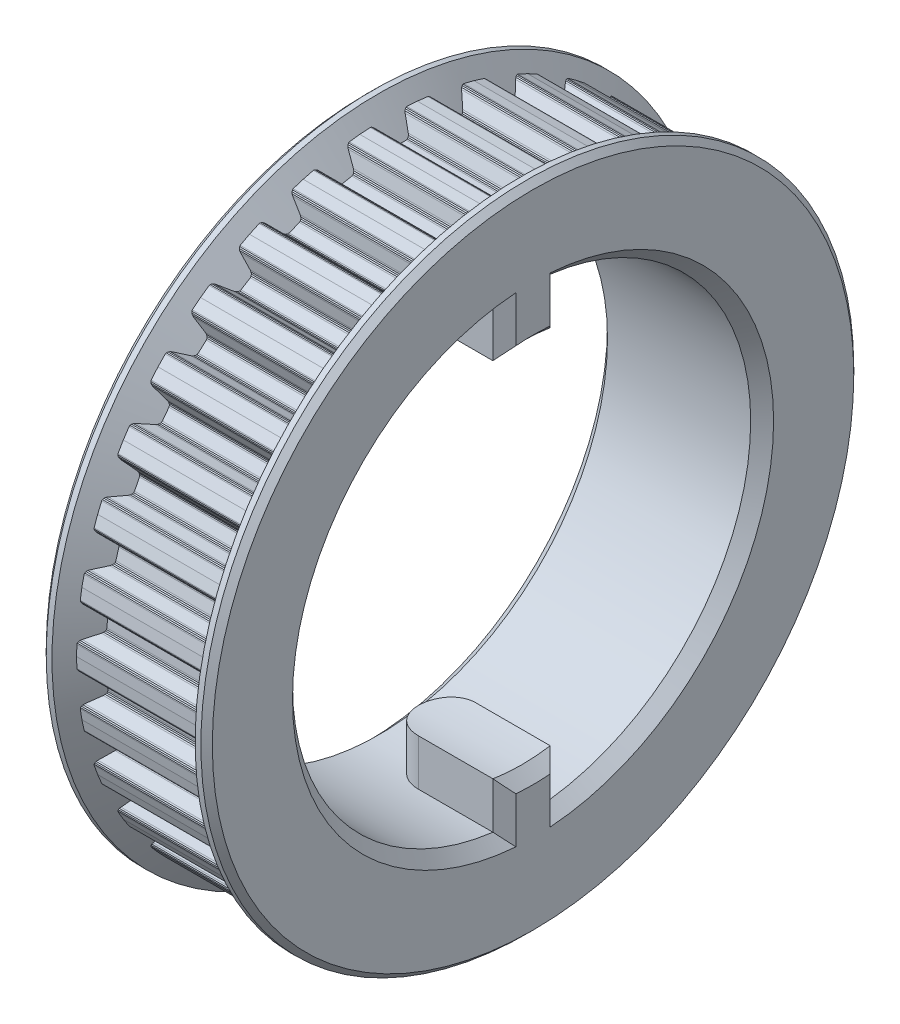
SolidWorks part; units mm, degrees
material "PLA"
ref_plane "Front Plane" through (0, 0, 0) normal (0, 0, 1) x (1, 0, 0)
ref_plane "Top Plane" through (0, 0, 0) normal (0, 1, 0) x (1, 0, 0)
ref_plane "Right Plane" through (0, 0, 0) normal (1, 0, 0) x (0, 0, -1)
sketch "Sketch1" plane through (0, 0, 0) normal (1, 0, 0) x (0, 0, -1)
  circle A1 centre (0, 0) radius 25.5
  dimension "D2" = 51
extrude "Boss-Extrude1" add sketch "Sketch1" along normal mid plane 12.5
sketch "Sketch2" plane through (6.25, 0, 0) normal (1, 0, 0) x (0, 0, -1)
  circle A7 centre (0, 0) radius 28.5
  circle A8 centre (0, 0) radius 28.5
  dimension "D1" = 3
extrude "Boss-Extrude2" add sketch "Sketch2" along normal blind 1
mirror "Mirror2" about plane through (0, 0, 0) normal (1, 0, 0) of "Boss-Extrude2"
sketch "Sketch3" plane through (7.25, 0, 0) normal (1, 0, 0) x (0, 0, -1)
  circle A0 centre (0, 0) radius 20
  dimension "D1" = 40
extrude "Cut-Extrude1" cut sketch "Sketch3" against normal through all
sketch "Sketch5" plane through (7.25, 0, 0) normal (1, 0, 0) x (0, 0, -1)
  line L1 (2.5, 28.3901) -> (-2.5, 28.3901)
  line L2 (2.5, 28.3901) -> (2.5, -28.3901)
  line L3 (2.5, -28.3901) -> (-2.5, -28.3901)
  line L4 (-2.5, 28.3901) -> (-2.5, -28.3901)
  line L5 (2.5, 28.3901) -> (-2.5, -28.3901) construction
  line L6 (2.5, -28.3901) -> (-2.5, 28.3901) construction
  circle A0 centre (0, 0) radius 28.5 construction
  circle A1 centre (0, 0) radius 16
  circle A2 centre (0, 0) radius 20 construction
  point P0 (0, 0)
  circle M5 centre (0, 0) radius 20
  dimension "D2" = 4
  dimension "D1" = 5
extrude "Boss-Extrude3" add sketch "Sketch5" against normal blind 10 contours A1 L4 L2 M5 | A1 L2 L4 M5 region at (7.25, 17.9411, 0) region at (7.25, -17.9411, 0)
fillet "Fillet1" radius 2.5 4 edges at (-2.75, 17.8233, 2.5) (-2.75, 17.8233, -2.5) (-2.75, -17.8233, -2.5) (-2.75, -17.8233, 2.5)
chamfer "Chamfer1" distance 3 angle 35 2 edges at (6.25, 0, -25.5) (-6.25, 0, -25.5) first distance on face at (6.25, 0, -25.5) first distance on face at (-6.25, 0, -25.5)
chamfer "Chamfer4" distance 1 angle 45 9 edges at (-7.25, 0, -20) (7.25, 0, 20) (7.25, 0, -20) (7.25, 17.8233, -2.5) (7.25, 16, 0) (7.25, 17.8233, 2.5) (7.25, -17.8233, 2.5) (7.25, -16, 0) (7.25, -17.8233, -2.5)
chamfer "Chamfer3" distance 0.5 angle 45 2 edges at (-7.25, 0, -28.5) (7.25, 0, -28.5)
sketch "Sketch6" plane through (0, 0, 0) normal (1, 0, 0) x (0, 0, -1)
  line L0 (2.5129, -27.119) -> (3.4233, -27.0134)
  line L1 (3.4233, -27.0134) -> (3.5073, -26.9837)
  line L2 (3.5073, -26.9837) -> (3.5995, -26.9145)
  line L3 (3.5995, -26.9145) -> (3.6697, -26.8197)
  line L4 (3.6697, -26.8197) -> (3.7127, -26.7044)
  line L5 (3.7127, -26.7044) -> (3.9415, -25.6841)
  line L6 (3.9415, -25.6841) -> (3.9845, -25.5692)
  line L7 (3.9845, -25.5692) -> (4.0547, -25.4743)
  line L8 (4.0547, -25.4743) -> (4.147, -25.4049)
  line L9 (4.147, -25.4049) -> (4.2565, -25.3661)
  line L10 (4.2565, -25.3661) -> (5.1942, -25.1908)
  line L11 (5.1942, -25.1908) -> (5.3104, -25.1874)
  line L12 (5.3104, -25.1874) -> (5.4215, -25.2188)
  line L13 (5.4215, -25.2188) -> (5.5212, -25.282)
  line L14 (5.5212, -25.282) -> (5.6028, -25.3736)
  line L15 (5.6028, -25.3736) -> (6.1847, -26.2423)
  line L16 (6.1847, -26.2423) -> (6.2666, -26.3342)
  line L17 (6.2666, -26.3342) -> (6.3663, -26.3973)
  line L18 (6.3663, -26.3973) -> (6.4774, -26.4285)
  line L19 (6.4774, -26.4285) -> (6.5663, -26.4259)
  line L20 (6.5663, -26.4259) -> (7.4533, -26.1955)
  line L21 (7.4533, -26.1955) -> (8.3287, -25.9245)
  line L22 (8.3287, -25.9245) -> (8.4058, -25.8798)
  line L23 (8.4058, -25.8798) -> (8.4838, -25.7948)
  line L24 (8.4838, -25.7948) -> (8.5353, -25.6887)
  line L25 (8.5353, -25.6887) -> (8.5564, -25.5675)
  line L26 (8.5564, -25.5675) -> (8.5939, -24.5226)
  line L27 (8.5939, -24.5226) -> (8.615, -24.4017)
  line L28 (8.615, -24.4017) -> (8.6665, -24.2956)
  line L29 (8.6665, -24.2956) -> (8.7445, -24.2103)
  line L30 (8.7445, -24.2103) -> (8.845, -24.152)
  line L31 (8.845, -24.152) -> (9.7346, -23.8074)
  line L32 (9.7346, -23.8074) -> (9.8481, -23.7828)
  line L33 (9.8481, -23.7828) -> (9.9632, -23.7932)
  line L34 (9.9632, -23.7932) -> (10.0727, -23.837)
  line L35 (10.0727, -23.837) -> (10.1698, -23.912)
  line L36 (10.1698, -23.912) -> (10.9014, -24.659)
  line L37 (10.9014, -24.659) -> (10.9988, -24.7344)
  line L38 (10.9988, -24.7344) -> (11.1084, -24.778)
  line L39 (11.1084, -24.778) -> (11.2233, -24.7883)
  line L40 (11.2233, -24.7883) -> (11.3102, -24.7694)
  line L41 (11.3102, -24.7694) -> (12.1398, -24.38)
  line L42 (12.1398, -24.38) -> (12.9505, -23.9527)
  line L43 (12.9505, -23.9527) -> (13.0181, -23.8946)
  line L44 (13.0181, -23.8946) -> (13.0791, -23.7967)
  line L45 (13.0791, -23.7967) -> (13.1103, -23.683)
  line L46 (13.1103, -23.683) -> (13.1087, -23.5599)
  line L47 (13.1087, -23.5599) -> (12.9536, -22.5259)
  line L48 (12.9536, -22.5259) -> (12.9521, -22.4032)
  line L49 (12.9521, -22.4032) -> (12.9833, -22.2894)
  line L50 (12.9833, -22.2894) -> (13.0443, -22.1913)
  line L51 (13.0443, -22.1913) -> (13.1323, -22.1155)
  line L52 (13.1323, -22.1155) -> (13.9434, -21.6133)
  line L53 (13.9434, -21.6133) -> (14.0505, -21.5683)
  line L54 (14.0505, -21.5683) -> (14.1655, -21.5574)
  line L55 (14.1655, -21.5574) -> (14.2813, -21.5802)
  line L56 (14.2813, -21.5802) -> (14.3905, -21.6362)
  line L57 (14.3905, -21.6362) -> (15.2469, -22.236)
  line L58 (15.2469, -22.236) -> (15.3564, -22.2922)
  line L59 (15.3564, -22.2922) -> (15.4722, -22.315)
  line L60 (15.4722, -22.315) -> (15.5871, -22.304)
  line L61 (15.5871, -22.304) -> (15.669, -22.2694)
  line L62 (15.669, -22.2694) -> (16.4129, -21.7342)
  line L63 (16.4129, -21.7342) -> (17.1313, -21.1652)
  line L64 (17.1313, -21.1652) -> (17.1871, -21.0957)
  line L65 (17.1871, -21.0957) -> (17.229, -20.9883)
  line L66 (17.229, -20.9883) -> (17.2388, -20.8707)
  line L67 (17.2388, -20.8707) -> (17.2147, -20.75)
  line L68 (17.2147, -20.75) -> (16.8721, -19.7621)
  line L69 (16.8721, -19.7621) -> (16.8482, -19.6418)
  line L70 (16.8482, -19.6418) -> (16.8579, -19.5242)
  line L71 (16.8579, -19.5242) -> (16.8998, -19.4166)
  line L72 (16.8998, -19.4166) -> (16.9724, -19.3259)
  line L73 (16.9724, -19.3259) -> (17.6775, -18.6832)
  line L74 (17.6775, -18.6832) -> (17.7744, -18.6192)
  line L75 (17.7744, -18.6192) -> (17.8855, -18.5874)
  line L76 (17.8855, -18.5874) -> (18.0034, -18.5886)
  line L77 (18.0034, -18.5886) -> (18.1211, -18.6236)
  line L78 (18.1211, -18.6236) -> (19.0731, -19.0558)
  line L79 (19.0731, -19.0558) -> (19.1911, -19.0909)
  line L80 (19.1911, -19.0909) -> (19.3091, -19.092)
  line L81 (19.3091, -19.092) -> (19.42, -19.0601)
  line L82 (19.42, -19.0601) -> (19.4942, -19.0111)
  line L83 (19.4942, -19.0111) -> (20.1271, -18.3483)
  line L84 (20.1271, -18.3483) -> (20.7287, -17.6569)
  line L85 (20.7287, -17.6569) -> (20.7707, -17.5784)
  line L86 (20.7707, -17.5784) -> (20.7923, -17.4651)
  line L87 (20.7923, -17.4651) -> (20.7802, -17.3477)
  line L88 (20.7802, -17.3477) -> (20.7344, -17.2335)
  line L89 (20.7344, -17.2335) -> (20.2161, -16.3254)
  line L90 (20.2161, -16.3254) -> (20.1705, -16.2115)
  line L91 (20.1705, -16.2115) -> (20.1584, -16.0942)
  line L92 (20.1584, -16.0942) -> (20.1798, -15.9806)
  line L93 (20.1798, -15.9806) -> (20.2346, -15.8782)
  line L94 (20.2346, -15.8782) -> (20.8095, -15.1169)
  line L95 (20.8095, -15.1169) -> (20.8931, -15.0362)
  line L96 (20.8931, -15.0362) -> (20.9964, -14.9845)
  line L97 (20.9964, -14.9845) -> (21.1126, -14.964)
  line L98 (21.1126, -14.964) -> (21.2346, -14.9767)
  line L99 (21.2346, -14.9767) -> (22.2499, -15.2267)
  line L100 (22.2499, -15.2267) -> (22.3723, -15.2395)
  line L101 (22.3723, -15.2395) -> (22.4885, -15.2189)
  line L102 (22.4885, -15.2189) -> (22.5916, -15.1671)
  line L103 (22.5916, -15.1671) -> (22.6556, -15.1053)
  line L104 (22.6556, -15.1053) -> (23.1559, -14.3375)
  line L105 (23.1559, -14.3375) -> (23.6202, -13.5474)
  line L106 (23.6202, -13.5474) -> (23.6471, -13.4625)
  line L107 (23.6471, -13.4625) -> (23.6474, -13.3471)
  line L108 (23.6474, -13.3471) -> (23.614, -13.234)
  line L109 (23.614, -13.234) -> (23.548, -13.1301)
  line L110 (23.548, -13.1301) -> (22.8717, -12.3327)
  line L111 (22.8717, -12.3327) -> (22.8059, -12.2292)
  line L112 (22.8059, -12.2292) -> (22.7725, -12.116)
  line L113 (22.7725, -12.116) -> (22.7727, -12.0005)
  line L114 (22.7727, -12.0005) -> (22.8077, -11.8897)
  line L115 (22.8077, -11.8897) -> (23.2329, -11.0357)
  line L116 (23.2329, -11.0357) -> (23.3002, -10.9411)
  line L117 (23.3002, -10.9411) -> (23.3923, -10.8713)
  line L118 (23.3923, -10.8713) -> (23.5027, -10.8298)
  line L119 (23.5027, -10.8298) -> (23.625, -10.8199)
  line L120 (23.625, -10.8199) -> (24.6689, -10.879)
  line L121 (24.6689, -10.879) -> (24.7916, -10.8691)
  line L122 (24.7916, -10.8691) -> (24.902, -10.8275)
  line L123 (24.902, -10.8275) -> (24.9939, -10.7577)
  line L124 (24.9939, -10.7577) -> (25.0454, -10.6852)
  line L125 (25.0454, -10.6852) -> (25.3961, -9.8385)
  line L126 (25.3961, -9.8385) -> (25.7073, -8.9765)
  line L127 (25.7073, -8.9765) -> (25.7182, -8.8881)
  line L128 (25.7182, -8.8881) -> (25.6973, -8.7746)
  line L129 (25.6973, -8.7746) -> (25.6437, -8.6696)
  line L130 (25.6437, -8.6696) -> (25.5597, -8.5797)
  line L131 (25.5597, -8.5797) -> (24.7484, -7.9201)
  line L132 (24.7484, -7.9201) -> (24.6647, -7.8304)
  line L133 (24.6647, -7.8304) -> (24.611, -7.7253)
  line L134 (24.611, -7.7253) -> (24.59, -7.6117)
  line L135 (24.59, -7.6117) -> (24.604, -7.4964)
  line L136 (24.604, -7.4964) -> (24.8651, -6.5788)
  line L137 (24.8651, -6.5788) -> (24.9139, -6.4734)
  line L138 (24.9139, -6.4734) -> (24.9916, -6.3879)
  line L139 (24.9916, -6.3879) -> (25.0925, -6.3267)
  line L140 (25.0925, -6.3267) -> (25.2109, -6.2946)
  line L141 (25.2109, -6.2946) -> (26.2479, -6.1609)
  line L142 (26.2479, -6.1609) -> (26.3667, -6.1286)
  line L143 (26.3667, -6.1286) -> (26.4676, -6.0674)
  line L144 (26.4676, -6.0674) -> (26.5451, -5.9819)
  line L145 (26.5451, -5.9819) -> (26.5824, -5.9011)
  line L146 (26.5824, -5.9011) -> (26.7715, -5.0045)
  line L147 (26.7715, -5.0045) -> (26.9191, -4.1)
  line L148 (26.9191, -4.1) -> (26.9135, -4.0111)
  line L149 (26.9135, -4.0111) -> (26.8721, -3.9034)
  line L150 (26.8721, -3.9034) -> (26.8001, -3.81)
  line L151 (26.8001, -3.81) -> (26.701, -3.737)
  line L152 (26.701, -3.737) -> (25.7823, -3.2377)
  line L153 (25.7823, -3.2377) -> (25.6835, -3.1649)
  line L154 (25.6835, -3.1649) -> (25.6115, -3.0715)
  line L155 (25.6115, -3.0715) -> (25.57, -2.9637)
  line L156 (25.57, -2.9637) -> (25.5626, -2.8478)
  line L157 (25.5626, -2.8478) -> (25.6506, -1.8978)
  line L158 (25.6506, -1.8978) -> (25.6792, -1.7852)
  line L159 (25.6792, -1.7852) -> (25.7398, -1.6869)
  line L160 (25.7398, -1.6869) -> (25.8278, -1.6083)
  line L161 (25.8278, -1.6083) -> (25.9383, -1.5549)
  line L162 (25.9383, -1.5549) -> (26.933, -1.2329)
  line L163 (26.933, -1.2329) -> (27.0439, -1.1794)
  line L164 (27.0439, -1.1794) -> (27.1318, -1.1007)
  line L165 (27.1318, -1.1007) -> (27.1923, -1.0024)
  line L166 (27.1923, -1.0024) -> (27.2141, -0.9162)
  line L167 (27.2141, -0.9162) -> (27.2352, 0)
  line L168 (27.2352, 0) -> (27.2141, 0.9162)
  line L169 (27.2141, 0.9162) -> (27.1922, 1.0026)
  line L170 (27.1922, 1.0026) -> (27.1318, 1.1008)
  line L171 (27.1318, 1.1008) -> (27.0439, 1.1794)
  line L172 (27.0439, 1.1794) -> (26.933, 1.2329)
  line L173 (26.933, 1.2329) -> (25.9383, 1.5549)
  line L174 (25.9383, 1.5549) -> (25.8278, 1.6083)
  line L175 (25.8278, 1.6083) -> (25.7398, 1.6869)
  line L176 (25.7398, 1.6869) -> (25.6792, 1.7852)
  line L177 (25.6792, 1.7852) -> (25.6506, 1.8978)
  line L178 (25.6506, 1.8978) -> (25.5626, 2.8478)
  line L179 (25.5626, 2.8478) -> (25.57, 2.9637)
  line L180 (25.57, 2.9637) -> (25.6115, 3.0715)
  line L181 (25.6115, 3.0715) -> (25.6835, 3.1649)
  line L182 (25.6835, 3.1649) -> (25.7823, 3.2377)
  line L183 (25.7823, 3.2377) -> (26.701, 3.737)
  line L184 (26.701, 3.737) -> (26.8001, 3.81)
  line L185 (26.8001, 3.81) -> (26.8721, 3.9035)
  line L186 (26.8721, 3.9035) -> (26.9135, 4.0112)
  line L187 (26.9135, 4.0112) -> (26.919, 4.1)
  line L188 (26.919, 4.1) -> (26.7715, 5.0045)
  line L189 (26.7715, 5.0045) -> (26.5824, 5.9012)
  line L190 (26.5824, 5.9012) -> (26.545, 5.9821)
  line L191 (26.545, 5.9821) -> (26.4675, 6.0675)
  line L192 (26.4675, 6.0675) -> (26.3667, 6.1286)
  line L193 (26.3667, 6.1286) -> (26.2479, 6.1609)
  line L194 (26.2479, 6.1609) -> (25.2109, 6.2946)
  line L195 (25.2109, 6.2946) -> (25.0925, 6.3267)
  line L196 (25.0925, 6.3267) -> (24.9916, 6.3879)
  line L197 (24.9916, 6.3879) -> (24.9139, 6.4734)
  line L198 (24.9139, 6.4734) -> (24.8651, 6.5788)
  line L199 (24.8651, 6.5788) -> (24.604, 7.4964)
  line L200 (24.604, 7.4964) -> (24.59, 7.6117)
  line L201 (24.59, 7.6117) -> (24.611, 7.7253)
  line L202 (24.611, 7.7253) -> (24.6647, 7.8304)
  line L203 (24.6647, 7.8304) -> (24.7484, 7.9201)
  line L204 (24.7484, 7.9201) -> (25.5597, 8.5797)
  line L205 (25.5597, 8.5797) -> (25.6437, 8.6697)
  line L206 (25.6437, 8.6697) -> (25.6973, 8.7748)
  line L207 (25.6973, 8.7748) -> (25.7181, 8.8883)
  line L208 (25.7181, 8.8883) -> (25.7073, 8.9765)
  line L209 (25.7073, 8.9765) -> (25.3961, 9.8385)
  line L210 (25.3961, 9.8385) -> (25.0454, 10.6852)
  line L211 (25.0454, 10.6852) -> (24.9939, 10.7578)
  line L212 (24.9939, 10.7578) -> (24.902, 10.8276)
  line L213 (24.902, 10.8276) -> (24.7916, 10.8691)
  line L214 (24.7916, 10.8691) -> (24.6689, 10.879)
  line L215 (24.6689, 10.879) -> (23.625, 10.8199)
  line L216 (23.625, 10.8199) -> (23.5027, 10.8298)
  line L217 (23.5027, 10.8298) -> (23.3923, 10.8713)
  line L218 (23.3923, 10.8713) -> (23.3002, 10.9411)
  line L219 (23.3002, 10.9411) -> (23.2329, 11.0357)
  line L220 (23.2329, 11.0357) -> (22.8077, 11.8897)
  line L221 (22.8077, 11.8897) -> (22.7727, 12.0005)
  line L222 (22.7727, 12.0005) -> (22.7725, 12.116)
  line L223 (22.7725, 12.116) -> (22.8059, 12.2292)
  line L224 (22.8059, 12.2292) -> (22.8717, 12.3327)
  line L225 (22.8717, 12.3327) -> (23.548, 13.1301)
  line L226 (23.548, 13.1301) -> (23.614, 13.2341)
  line L227 (23.614, 13.2341) -> (23.6474, 13.3472)
  line L228 (23.6474, 13.3472) -> (23.647, 13.4626)
  line L229 (23.647, 13.4626) -> (23.6202, 13.5474)
  line L230 (23.6202, 13.5474) -> (23.1559, 14.3375)
  line L231 (23.1559, 14.3375) -> (22.6555, 15.1053)
  line L232 (22.6555, 15.1053) -> (22.5915, 15.1673)
  line L233 (22.5915, 15.1673) -> (22.4884, 15.219)
  line L234 (22.4884, 15.219) -> (22.3723, 15.2395)
  line L235 (22.3723, 15.2395) -> (22.2499, 15.2267)
  line L236 (22.2499, 15.2267) -> (21.2346, 14.9767)
  line L237 (21.2346, 14.9767) -> (21.1126, 14.964)
  line L238 (21.1126, 14.964) -> (20.9964, 14.9845)
  line L239 (20.9964, 14.9845) -> (20.8931, 15.0362)
  line L240 (20.8931, 15.0362) -> (20.8095, 15.1169)
  line L241 (20.8095, 15.1169) -> (20.2346, 15.8782)
  line L242 (20.2346, 15.8782) -> (20.1798, 15.9806)
  line L243 (20.1798, 15.9806) -> (20.1584, 16.0942)
  line L244 (20.1584, 16.0942) -> (20.1705, 16.2115)
  line L245 (20.1705, 16.2115) -> (20.2161, 16.3254)
  line L246 (20.2161, 16.3254) -> (20.7344, 17.2335)
  line L247 (20.7344, 17.2335) -> (20.7802, 17.3478)
  line L248 (20.7802, 17.3478) -> (20.7922, 17.4652)
  line L249 (20.7922, 17.4652) -> (20.7706, 17.5785)
  line L250 (20.7706, 17.5785) -> (20.7287, 17.6569)
  line L251 (20.7287, 17.6569) -> (20.1271, 18.3483)
  line L252 (20.1271, 18.3483) -> (19.4942, 19.0111)
  line L253 (19.4942, 19.0111) -> (19.4199, 19.0602)
  line L254 (19.4199, 19.0602) -> (19.309, 19.0921)
  line L255 (19.309, 19.0921) -> (19.1911, 19.0909)
  line L256 (19.1911, 19.0909) -> (19.0731, 19.0558)
  line L257 (19.0731, 19.0558) -> (18.1211, 18.6236)
  line L258 (18.1211, 18.6236) -> (18.0034, 18.5886)
  line L259 (18.0034, 18.5886) -> (17.8855, 18.5874)
  line L260 (17.8855, 18.5874) -> (17.7744, 18.6192)
  line L261 (17.7744, 18.6192) -> (17.6775, 18.6832)
  line L262 (17.6775, 18.6832) -> (16.9724, 19.3259)
  line L263 (16.9724, 19.3259) -> (16.8998, 19.4166)
  line L264 (16.8998, 19.4166) -> (16.8579, 19.5242)
  line L265 (16.8579, 19.5242) -> (16.8482, 19.6418)
  line L266 (16.8482, 19.6418) -> (16.8721, 19.7621)
  line L267 (16.8721, 19.7621) -> (17.2147, 20.75)
  line L268 (17.2147, 20.75) -> (17.2387, 20.8708)
  line L269 (17.2387, 20.8708) -> (17.2289, 20.9883)
  line L270 (17.2289, 20.9883) -> (17.1869, 21.0958)
  line L271 (17.1869, 21.0958) -> (17.1313, 21.1652)
  line L272 (17.1313, 21.1652) -> (16.4129, 21.7342)
  line L273 (16.4129, 21.7342) -> (15.669, 22.2694)
  line L274 (15.669, 22.2694) -> (15.5869, 22.3041)
  line L275 (15.5869, 22.3041) -> (15.4721, 22.315)
  line L276 (15.4721, 22.315) -> (15.3564, 22.2922)
  line L277 (15.3564, 22.2922) -> (15.2469, 22.236)
  line L278 (15.2469, 22.236) -> (14.3905, 21.6362)
  line L279 (14.3905, 21.6362) -> (14.2813, 21.5802)
  line L280 (14.2813, 21.5802) -> (14.1655, 21.5574)
  line L281 (14.1655, 21.5574) -> (14.0505, 21.5683)
  line L282 (14.0505, 21.5683) -> (13.9434, 21.6133)
  line L283 (13.9434, 21.6133) -> (13.1323, 22.1155)
  line L284 (13.1323, 22.1155) -> (13.0443, 22.1913)
  line L285 (13.0443, 22.1913) -> (12.9833, 22.2894)
  line L286 (12.9833, 22.2894) -> (12.9521, 22.4032)
  line L287 (12.9521, 22.4032) -> (12.9536, 22.5259)
  line L288 (12.9536, 22.5259) -> (13.1087, 23.5599)
  line L289 (13.1087, 23.5599) -> (13.1102, 23.683)
  line L290 (13.1102, 23.683) -> (13.079, 23.7968)
  line L291 (13.079, 23.7968) -> (13.0179, 23.8947)
  line L292 (13.0179, 23.8947) -> (12.9505, 23.9527)
  line L293 (12.9505, 23.9527) -> (12.1398, 24.38)
  line L294 (12.1398, 24.38) -> (11.3102, 24.7694)
  line L295 (11.3102, 24.7694) -> (11.2232, 24.7884)
  line L296 (11.2232, 24.7884) -> (11.1083, 24.7781)
  line L297 (11.1083, 24.7781) -> (10.9987, 24.7344)
  line L298 (10.9987, 24.7344) -> (10.9014, 24.659)
  line L299 (10.9014, 24.659) -> (10.1698, 23.912)
  line L300 (10.1698, 23.912) -> (10.0727, 23.837)
  line L301 (10.0727, 23.837) -> (9.9632, 23.7932)
  line L302 (9.9632, 23.7932) -> (9.8481, 23.7828)
  line L303 (9.8481, 23.7828) -> (9.7346, 23.8074)
  line L304 (9.7346, 23.8074) -> (8.845, 24.152)
  line L305 (8.845, 24.152) -> (8.7445, 24.2103)
  line L306 (8.7445, 24.2103) -> (8.6665, 24.2956)
  line L307 (8.6665, 24.2956) -> (8.615, 24.4017)
  line L308 (8.615, 24.4017) -> (8.5939, 24.5226)
  line L309 (8.5939, 24.5226) -> (8.5564, 25.5675)
  line L310 (8.5564, 25.5675) -> (8.5352, 25.6888)
  line L311 (8.5352, 25.6888) -> (8.4836, 25.7948)
  line L312 (8.4836, 25.7948) -> (8.4057, 25.8799)
  line L313 (8.4057, 25.8799) -> (8.3287, 25.9245)
  line L314 (8.3287, 25.9245) -> (7.4533, 26.1955)
  line L315 (7.4533, 26.1955) -> (6.5663, 26.4259)
  line L316 (6.5663, 26.4259) -> (6.4772, 26.4286)
  line L317 (6.4772, 26.4286) -> (6.3662, 26.3973)
  line L318 (6.3662, 26.3973) -> (6.2665, 26.3343)
  line L319 (6.2665, 26.3343) -> (6.1847, 26.2423)
  line L320 (6.1847, 26.2423) -> (5.6028, 25.3736)
  line L321 (5.6028, 25.3736) -> (5.5212, 25.282)
  line L322 (5.5212, 25.282) -> (5.4215, 25.2188)
  line L323 (5.4215, 25.2188) -> (5.3104, 25.1874)
  line L324 (5.3104, 25.1874) -> (5.1942, 25.1908)
  line L325 (5.1942, 25.1908) -> (4.2565, 25.3661)
  line L326 (4.2565, 25.3661) -> (4.147, 25.4049)
  line L327 (4.147, 25.4049) -> (4.0547, 25.4743)
  line L328 (4.0547, 25.4743) -> (3.9845, 25.5692)
  line L329 (3.9845, 25.5692) -> (3.9415, 25.6841)
  line L330 (3.9415, 25.6841) -> (3.7127, 26.7044)
  line L331 (3.7127, 26.7044) -> (3.6696, 26.8197)
  line L332 (3.6696, 26.8197) -> (3.5994, 26.9145)
  line L333 (3.5994, 26.9145) -> (3.5071, 26.9838)
  line L334 (3.5071, 26.9838) -> (3.4232, 27.0134)
  line L335 (3.4232, 27.0134) -> (2.5129, 27.119)
  line L336 (2.5129, 27.119) -> (1.5987, 27.1825)
  line L337 (1.5987, 27.1825) -> (1.5107, 27.1688)
  line L338 (1.5107, 27.1688) -> (1.4073, 27.1176)
  line L339 (1.4073, 27.1176) -> (1.3209, 27.0373)
  line L340 (1.3209, 27.0373) -> (1.2574, 26.9319)
  line L341 (1.2574, 26.9319) -> (0.845, 25.9711)
  line L342 (0.845, 25.9711) -> (0.7816, 25.866)
  line L343 (0.7816, 25.866) -> (0.6953, 25.7856)
  line L344 (0.6953, 25.7856) -> (0.5918, 25.7343)
  line L345 (0.5918, 25.7343) -> (0.477, 25.7163)
  line L346 (0.477, 25.7163) -> (-0.477, 25.7163)
  line L347 (-0.477, 25.7163) -> (-0.5918, 25.7343)
  line L348 (-0.5918, 25.7343) -> (-0.6953, 25.7856)
  line L349 (-0.6953, 25.7856) -> (-0.7816, 25.866)
  line L350 (-0.7816, 25.866) -> (-0.845, 25.9711)
  line L351 (-0.845, 25.9711) -> (-1.2574, 26.9319)
  line L352 (-1.2574, 26.9319) -> (-1.321, 27.0373)
  line L353 (-1.321, 27.0373) -> (-1.4074, 27.1176)
  line L354 (-1.4074, 27.1176) -> (-1.5109, 27.1688)
  line L355 (-1.5109, 27.1688) -> (-1.5987, 27.1825)
  line L356 (-1.5987, 27.1825) -> (-2.5129, 27.119)
  line L357 (-2.5129, 27.119) -> (-3.4233, 27.0134)
  line L358 (-3.4233, 27.0134) -> (-3.5073, 26.9837)
  line L359 (-3.5073, 26.9837) -> (-3.5995, 26.9145)
  line L360 (-3.5995, 26.9145) -> (-3.6697, 26.8197)
  line L361 (-3.6697, 26.8197) -> (-3.7127, 26.7044)
  line L362 (-3.7127, 26.7044) -> (-3.9415, 25.6841)
  line L363 (-3.9415, 25.6841) -> (-3.9845, 25.5692)
  line L364 (-3.9845, 25.5692) -> (-4.0547, 25.4743)
  line L365 (-4.0547, 25.4743) -> (-4.147, 25.4049)
  line L366 (-4.147, 25.4049) -> (-4.2565, 25.3661)
  line L367 (-4.2565, 25.3661) -> (-5.1942, 25.1908)
  line L368 (-5.1942, 25.1908) -> (-5.3104, 25.1874)
  line L369 (-5.3104, 25.1874) -> (-5.4215, 25.2188)
  line L370 (-5.4215, 25.2188) -> (-5.5212, 25.282)
  line L371 (-5.5212, 25.282) -> (-5.6028, 25.3736)
  line L372 (-5.6028, 25.3736) -> (-6.1847, 26.2423)
  line L373 (-6.1847, 26.2423) -> (-6.2666, 26.3342)
  line L374 (-6.2666, 26.3342) -> (-6.3663, 26.3973)
  line L375 (-6.3663, 26.3973) -> (-6.4774, 26.4285)
  line L376 (-6.4774, 26.4285) -> (-6.5663, 26.4259)
  line L377 (-6.5663, 26.4259) -> (-7.4533, 26.1955)
  line L378 (-7.4533, 26.1955) -> (-8.3287, 25.9245)
  line L379 (-8.3287, 25.9245) -> (-8.4058, 25.8798)
  line L380 (-8.4058, 25.8798) -> (-8.4838, 25.7948)
  line L381 (-8.4838, 25.7948) -> (-8.5353, 25.6887)
  line L382 (-8.5353, 25.6887) -> (-8.5564, 25.5675)
  line L383 (-8.5564, 25.5675) -> (-8.5939, 24.5226)
  line L384 (-8.5939, 24.5226) -> (-8.615, 24.4017)
  line L385 (-8.615, 24.4017) -> (-8.6665, 24.2956)
  line L386 (-8.6665, 24.2956) -> (-8.7445, 24.2103)
  line L387 (-8.7445, 24.2103) -> (-8.845, 24.152)
  line L388 (-8.845, 24.152) -> (-9.7346, 23.8074)
  line L389 (-9.7346, 23.8074) -> (-9.8481, 23.7828)
  line L390 (-9.8481, 23.7828) -> (-9.9632, 23.7932)
  line L391 (-9.9632, 23.7932) -> (-10.0727, 23.837)
  line L392 (-10.0727, 23.837) -> (-10.1698, 23.912)
  line L393 (-10.1698, 23.912) -> (-10.9014, 24.659)
  line L394 (-10.9014, 24.659) -> (-10.9988, 24.7344)
  line L395 (-10.9988, 24.7344) -> (-11.1084, 24.778)
  line L396 (-11.1084, 24.778) -> (-11.2233, 24.7883)
  line L397 (-11.2233, 24.7883) -> (-11.3102, 24.7694)
  line L398 (-11.3102, 24.7694) -> (-12.1398, 24.38)
  line L399 (-12.1398, 24.38) -> (-12.9505, 23.9527)
  line L400 (-12.9505, 23.9527) -> (-13.0181, 23.8946)
  line L401 (-13.0181, 23.8946) -> (-13.0791, 23.7967)
  line L402 (-13.0791, 23.7967) -> (-13.1103, 23.683)
  line L403 (-13.1103, 23.683) -> (-13.1087, 23.5599)
  line L404 (-13.1087, 23.5599) -> (-12.9536, 22.5259)
  line L405 (-12.9536, 22.5259) -> (-12.9521, 22.4032)
  line L406 (-12.9521, 22.4032) -> (-12.9833, 22.2894)
  line L407 (-12.9833, 22.2894) -> (-13.0443, 22.1913)
  line L408 (-13.0443, 22.1913) -> (-13.1323, 22.1155)
  line L409 (-13.1323, 22.1155) -> (-13.9434, 21.6133)
  line L410 (-13.9434, 21.6133) -> (-14.0505, 21.5683)
  line L411 (-14.0505, 21.5683) -> (-14.1655, 21.5574)
  line L412 (-14.1655, 21.5574) -> (-14.2813, 21.5802)
  line L413 (-14.2813, 21.5802) -> (-14.3905, 21.6362)
  line L414 (-14.3905, 21.6362) -> (-15.2469, 22.236)
  line L415 (-15.2469, 22.236) -> (-15.3564, 22.2922)
  line L416 (-15.3564, 22.2922) -> (-15.4722, 22.315)
  line L417 (-15.4722, 22.315) -> (-15.5871, 22.304)
  line L418 (-15.5871, 22.304) -> (-15.669, 22.2694)
  line L419 (-15.669, 22.2694) -> (-16.4129, 21.7342)
  line L420 (-16.4129, 21.7342) -> (-17.1313, 21.1652)
  line L421 (-17.1313, 21.1652) -> (-17.1871, 21.0957)
  line L422 (-17.1871, 21.0957) -> (-17.229, 20.9883)
  line L423 (-17.229, 20.9883) -> (-17.2388, 20.8707)
  line L424 (-17.2388, 20.8707) -> (-17.2147, 20.75)
  line L425 (-17.2147, 20.75) -> (-16.8721, 19.7621)
  line L426 (-16.8721, 19.7621) -> (-16.8482, 19.6418)
  line L427 (-16.8482, 19.6418) -> (-16.8579, 19.5242)
  line L428 (-16.8579, 19.5242) -> (-16.8998, 19.4166)
  line L429 (-16.8998, 19.4166) -> (-16.9724, 19.3259)
  line L430 (-16.9724, 19.3259) -> (-17.6775, 18.6832)
  line L431 (-17.6775, 18.6832) -> (-17.7744, 18.6192)
  line L432 (-17.7744, 18.6192) -> (-17.8855, 18.5874)
  line L433 (-17.8855, 18.5874) -> (-18.0034, 18.5886)
  line L434 (-18.0034, 18.5886) -> (-18.1211, 18.6236)
  line L435 (-18.1211, 18.6236) -> (-19.0731, 19.0558)
  line L436 (-19.0731, 19.0558) -> (-19.1911, 19.0909)
  line L437 (-19.1911, 19.0909) -> (-19.3091, 19.092)
  line L438 (-19.3091, 19.092) -> (-19.42, 19.0601)
  line L439 (-19.42, 19.0601) -> (-19.4942, 19.0111)
  line L440 (-19.4942, 19.0111) -> (-20.1271, 18.3483)
  line L441 (-20.1271, 18.3483) -> (-20.7287, 17.6569)
  line L442 (-20.7287, 17.6569) -> (-20.7707, 17.5784)
  line L443 (-20.7707, 17.5784) -> (-20.7923, 17.4651)
  line L444 (-20.7923, 17.4651) -> (-20.7802, 17.3477)
  line L445 (-20.7802, 17.3477) -> (-20.7344, 17.2335)
  line L446 (-20.7344, 17.2335) -> (-20.2161, 16.3254)
  line L447 (-20.2161, 16.3254) -> (-20.1705, 16.2115)
  line L448 (-20.1705, 16.2115) -> (-20.1584, 16.0942)
  line L449 (-20.1584, 16.0942) -> (-20.1798, 15.9806)
  line L450 (-20.1798, 15.9806) -> (-20.2346, 15.8782)
  line L451 (-20.2346, 15.8782) -> (-20.8095, 15.1169)
  line L452 (-20.8095, 15.1169) -> (-20.8931, 15.0362)
  line L453 (-20.8931, 15.0362) -> (-20.9964, 14.9845)
  line L454 (-20.9964, 14.9845) -> (-21.1126, 14.964)
  line L455 (-21.1126, 14.964) -> (-21.2346, 14.9767)
  line L456 (-21.2346, 14.9767) -> (-22.2499, 15.2267)
  line L457 (-22.2499, 15.2267) -> (-22.3723, 15.2395)
  line L458 (-22.3723, 15.2395) -> (-22.4885, 15.2189)
  line L459 (-22.4885, 15.2189) -> (-22.5916, 15.1671)
  line L460 (-22.5916, 15.1671) -> (-22.6556, 15.1053)
  line L461 (-22.6556, 15.1053) -> (-23.1559, 14.3375)
  line L462 (-23.1559, 14.3375) -> (-23.6202, 13.5474)
  line L463 (-23.6202, 13.5474) -> (-23.6471, 13.4625)
  line L464 (-23.6471, 13.4625) -> (-23.6474, 13.3471)
  line L465 (-23.6474, 13.3471) -> (-23.614, 13.234)
  line L466 (-23.614, 13.234) -> (-23.548, 13.1301)
  line L467 (-23.548, 13.1301) -> (-22.8717, 12.3327)
  line L468 (-22.8717, 12.3327) -> (-22.8059, 12.2292)
  line L469 (-22.8059, 12.2292) -> (-22.7725, 12.116)
  line L470 (-22.7725, 12.116) -> (-22.7727, 12.0005)
  line L471 (-22.7727, 12.0005) -> (-22.8077, 11.8897)
  line L472 (-22.8077, 11.8897) -> (-23.2329, 11.0357)
  line L473 (-23.2329, 11.0357) -> (-23.3002, 10.9411)
  line L474 (-23.3002, 10.9411) -> (-23.3923, 10.8713)
  line L475 (-23.3923, 10.8713) -> (-23.5027, 10.8298)
  line L476 (-23.5027, 10.8298) -> (-23.625, 10.8199)
  line L477 (-23.625, 10.8199) -> (-24.6689, 10.879)
  line L478 (-24.6689, 10.879) -> (-24.7916, 10.8691)
  line L479 (-24.7916, 10.8691) -> (-24.902, 10.8275)
  line L480 (-24.902, 10.8275) -> (-24.9939, 10.7577)
  line L481 (-24.9939, 10.7577) -> (-25.0454, 10.6852)
  line L482 (-25.0454, 10.6852) -> (-25.3961, 9.8385)
  line L483 (-25.3961, 9.8385) -> (-25.7073, 8.9765)
  line L484 (-25.7073, 8.9765) -> (-25.7182, 8.8881)
  line L485 (-25.7182, 8.8881) -> (-25.6973, 8.7746)
  line L486 (-25.6973, 8.7746) -> (-25.6437, 8.6696)
  line L487 (-25.6437, 8.6696) -> (-25.5597, 8.5797)
  line L488 (-25.5597, 8.5797) -> (-24.7484, 7.9201)
  line L489 (-24.7484, 7.9201) -> (-24.6647, 7.8304)
  line L490 (-24.6647, 7.8304) -> (-24.611, 7.7253)
  line L491 (-24.611, 7.7253) -> (-24.59, 7.6117)
  line L492 (-24.59, 7.6117) -> (-24.604, 7.4964)
  line L493 (-24.604, 7.4964) -> (-24.8651, 6.5788)
  line L494 (-24.8651, 6.5788) -> (-24.9139, 6.4734)
  line L495 (-24.9139, 6.4734) -> (-24.9916, 6.3879)
  line L496 (-24.9916, 6.3879) -> (-25.0925, 6.3267)
  line L497 (-25.0925, 6.3267) -> (-25.2109, 6.2946)
  line L498 (-25.2109, 6.2946) -> (-26.2479, 6.1609)
  line L499 (-26.2479, 6.1609) -> (-26.3667, 6.1286)
  line L500 (-26.3667, 6.1286) -> (-26.4676, 6.0674)
  line L501 (-26.4676, 6.0674) -> (-26.5451, 5.9819)
  line L502 (-26.5451, 5.9819) -> (-26.5824, 5.9011)
  line L503 (-26.5824, 5.9011) -> (-26.7715, 5.0045)
  line L504 (-26.7715, 5.0045) -> (-26.9191, 4.1)
  line L505 (-26.9191, 4.1) -> (-26.9135, 4.0111)
  line L506 (-26.9135, 4.0111) -> (-26.8721, 3.9034)
  line L507 (-26.8721, 3.9034) -> (-26.8001, 3.81)
  line L508 (-26.8001, 3.81) -> (-26.701, 3.737)
  line L509 (-26.701, 3.737) -> (-25.7823, 3.2377)
  line L510 (-25.7823, 3.2377) -> (-25.6835, 3.1649)
  line L511 (-25.6835, 3.1649) -> (-25.6115, 3.0715)
  line L512 (-25.6115, 3.0715) -> (-25.57, 2.9637)
  line L513 (-25.57, 2.9637) -> (-25.5626, 2.8478)
  line L514 (-25.5626, 2.8478) -> (-25.6506, 1.8978)
  line L515 (-25.6506, 1.8978) -> (-25.6792, 1.7852)
  line L516 (-25.6792, 1.7852) -> (-25.7398, 1.6869)
  line L517 (-25.7398, 1.6869) -> (-25.8278, 1.6083)
  line L518 (-25.8278, 1.6083) -> (-25.9383, 1.5549)
  line L519 (-25.9383, 1.5549) -> (-26.933, 1.2329)
  line L520 (-26.933, 1.2329) -> (-27.0439, 1.1794)
  line L521 (-27.0439, 1.1794) -> (-27.1318, 1.1007)
  line L522 (-27.1318, 1.1007) -> (-27.1923, 1.0024)
  line L523 (-27.1923, 1.0024) -> (-27.2141, 0.9162)
  line L524 (-27.2141, 0.9162) -> (-27.2352, 0)
  line L525 (-27.2352, 0) -> (-27.2141, -0.9162)
  line L526 (-27.2141, -0.9162) -> (-27.1922, -1.0026)
  line L527 (-27.1922, -1.0026) -> (-27.1318, -1.1008)
  line L528 (-27.1318, -1.1008) -> (-27.0439, -1.1794)
  line L529 (-27.0439, -1.1794) -> (-26.933, -1.2329)
  line L530 (-26.933, -1.2329) -> (-25.9383, -1.5549)
  line L531 (-25.9383, -1.5549) -> (-25.8278, -1.6083)
  line L532 (-25.8278, -1.6083) -> (-25.7398, -1.6869)
  line L533 (-25.7398, -1.6869) -> (-25.6792, -1.7852)
  line L534 (-25.6792, -1.7852) -> (-25.6506, -1.8978)
  line L535 (-25.6506, -1.8978) -> (-25.5626, -2.8478)
  line L536 (-25.5626, -2.8478) -> (-25.57, -2.9637)
  line L537 (-25.57, -2.9637) -> (-25.6115, -3.0715)
  line L538 (-25.6115, -3.0715) -> (-25.6835, -3.1649)
  line L539 (-25.6835, -3.1649) -> (-25.7823, -3.2377)
  line L540 (-25.7823, -3.2377) -> (-26.701, -3.737)
  line L541 (-26.701, -3.737) -> (-26.8001, -3.81)
  line L542 (-26.8001, -3.81) -> (-26.8721, -3.9035)
  line L543 (-26.8721, -3.9035) -> (-26.9135, -4.0112)
  line L544 (-26.9135, -4.0112) -> (-26.919, -4.1)
  line L545 (-26.919, -4.1) -> (-26.7715, -5.0045)
  line L546 (-26.7715, -5.0045) -> (-26.5824, -5.9012)
  line L547 (-26.5824, -5.9012) -> (-26.545, -5.9821)
  line L548 (-26.545, -5.9821) -> (-26.4675, -6.0675)
  line L549 (-26.4675, -6.0675) -> (-26.3667, -6.1286)
  line L550 (-26.3667, -6.1286) -> (-26.2479, -6.1609)
  line L551 (-26.2479, -6.1609) -> (-25.2109, -6.2946)
  line L552 (-25.2109, -6.2946) -> (-25.0925, -6.3267)
  line L553 (-25.0925, -6.3267) -> (-24.9916, -6.3879)
  line L554 (-24.9916, -6.3879) -> (-24.9139, -6.4734)
  line L555 (-24.9139, -6.4734) -> (-24.8651, -6.5788)
  line L556 (-24.8651, -6.5788) -> (-24.604, -7.4964)
  line L557 (-24.604, -7.4964) -> (-24.59, -7.6117)
  line L558 (-24.59, -7.6117) -> (-24.611, -7.7253)
  line L559 (-24.611, -7.7253) -> (-24.6647, -7.8304)
  line L560 (-24.6647, -7.8304) -> (-24.7484, -7.9201)
  line L561 (-24.7484, -7.9201) -> (-25.5597, -8.5797)
  line L562 (-25.5597, -8.5797) -> (-25.6437, -8.6697)
  line L563 (-25.6437, -8.6697) -> (-25.6973, -8.7748)
  line L564 (-25.6973, -8.7748) -> (-25.7181, -8.8883)
  line L565 (-25.7181, -8.8883) -> (-25.7073, -8.9765)
  line L566 (-25.7073, -8.9765) -> (-25.3961, -9.8385)
  line L567 (-25.3961, -9.8385) -> (-25.0454, -10.6852)
  line L568 (-25.0454, -10.6852) -> (-24.9939, -10.7578)
  line L569 (-24.9939, -10.7578) -> (-24.902, -10.8276)
  line L570 (-24.902, -10.8276) -> (-24.7916, -10.8691)
  line L571 (-24.7916, -10.8691) -> (-24.6689, -10.879)
  line L572 (-24.6689, -10.879) -> (-23.625, -10.8199)
  line L573 (-23.625, -10.8199) -> (-23.5027, -10.8298)
  line L574 (-23.5027, -10.8298) -> (-23.3923, -10.8713)
  line L575 (-23.3923, -10.8713) -> (-23.3002, -10.9411)
  line L576 (-23.3002, -10.9411) -> (-23.2329, -11.0357)
  line L577 (-23.2329, -11.0357) -> (-22.8077, -11.8897)
  line L578 (-22.8077, -11.8897) -> (-22.7727, -12.0005)
  line L579 (-22.7727, -12.0005) -> (-22.7725, -12.116)
  line L580 (-22.7725, -12.116) -> (-22.8059, -12.2292)
  line L581 (-22.8059, -12.2292) -> (-22.8717, -12.3327)
  line L582 (-22.8717, -12.3327) -> (-23.548, -13.1301)
  line L583 (-23.548, -13.1301) -> (-23.614, -13.2341)
  line L584 (-23.614, -13.2341) -> (-23.6474, -13.3472)
  line L585 (-23.6474, -13.3472) -> (-23.647, -13.4626)
  line L586 (-23.647, -13.4626) -> (-23.6202, -13.5474)
  line L587 (-23.6202, -13.5474) -> (-23.1559, -14.3375)
  line L588 (-23.1559, -14.3375) -> (-22.6555, -15.1053)
  line L589 (-22.6555, -15.1053) -> (-22.5915, -15.1673)
  line L590 (-22.5915, -15.1673) -> (-22.4884, -15.219)
  line L591 (-22.4884, -15.219) -> (-22.3723, -15.2395)
  line L592 (-22.3723, -15.2395) -> (-22.2499, -15.2267)
  line L593 (-22.2499, -15.2267) -> (-21.2346, -14.9767)
  line L594 (-21.2346, -14.9767) -> (-21.1126, -14.964)
  line L595 (-21.1126, -14.964) -> (-20.9964, -14.9845)
  line L596 (-20.9964, -14.9845) -> (-20.8931, -15.0362)
  line L597 (-20.8931, -15.0362) -> (-20.8095, -15.1169)
  line L598 (-20.8095, -15.1169) -> (-20.2346, -15.8782)
  line L599 (-20.2346, -15.8782) -> (-20.1798, -15.9806)
  line L600 (-20.1798, -15.9806) -> (-20.1584, -16.0942)
  line L601 (-20.1584, -16.0942) -> (-20.1705, -16.2115)
  line L602 (-20.1705, -16.2115) -> (-20.2161, -16.3254)
  line L603 (-20.2161, -16.3254) -> (-20.7344, -17.2335)
  line L604 (-20.7344, -17.2335) -> (-20.7802, -17.3478)
  line L605 (-20.7802, -17.3478) -> (-20.7922, -17.4652)
  line L606 (-20.7922, -17.4652) -> (-20.7706, -17.5785)
  line L607 (-20.7706, -17.5785) -> (-20.7287, -17.6569)
  line L608 (-20.7287, -17.6569) -> (-20.1271, -18.3483)
  line L609 (-20.1271, -18.3483) -> (-19.4942, -19.0111)
  line L610 (-19.4942, -19.0111) -> (-19.4199, -19.0602)
  line L611 (-19.4199, -19.0602) -> (-19.309, -19.0921)
  line L612 (-19.309, -19.0921) -> (-19.1911, -19.0909)
  line L613 (-19.1911, -19.0909) -> (-19.0731, -19.0558)
  line L614 (-19.0731, -19.0558) -> (-18.1211, -18.6236)
  line L615 (-18.1211, -18.6236) -> (-18.0034, -18.5886)
  line L616 (-18.0034, -18.5886) -> (-17.8855, -18.5874)
  line L617 (-17.8855, -18.5874) -> (-17.7744, -18.6192)
  line L618 (-17.7744, -18.6192) -> (-17.6775, -18.6832)
  line L619 (-17.6775, -18.6832) -> (-16.9724, -19.3259)
  line L620 (-16.9724, -19.3259) -> (-16.8998, -19.4166)
  line L621 (-16.8998, -19.4166) -> (-16.8579, -19.5242)
  line L622 (-16.8579, -19.5242) -> (-16.8482, -19.6418)
  line L623 (-16.8482, -19.6418) -> (-16.8721, -19.7621)
  line L624 (-16.8721, -19.7621) -> (-17.2147, -20.75)
  line L625 (-17.2147, -20.75) -> (-17.2387, -20.8708)
  line L626 (-17.2387, -20.8708) -> (-17.2289, -20.9883)
  line L627 (-17.2289, -20.9883) -> (-17.1869, -21.0958)
  line L628 (-17.1869, -21.0958) -> (-17.1313, -21.1652)
  line L629 (-17.1313, -21.1652) -> (-16.4129, -21.7342)
  line L630 (-16.4129, -21.7342) -> (-15.669, -22.2694)
  line L631 (-15.669, -22.2694) -> (-15.5869, -22.3041)
  line L632 (-15.5869, -22.3041) -> (-15.4721, -22.315)
  line L633 (-15.4721, -22.315) -> (-15.3564, -22.2922)
  line L634 (-15.3564, -22.2922) -> (-15.2469, -22.236)
  line L635 (-15.2469, -22.236) -> (-14.3905, -21.6362)
  line L636 (-14.3905, -21.6362) -> (-14.2813, -21.5802)
  line L637 (-14.2813, -21.5802) -> (-14.1655, -21.5574)
  line L638 (-14.1655, -21.5574) -> (-14.0505, -21.5683)
  line L639 (-14.0505, -21.5683) -> (-13.9434, -21.6133)
  line L640 (-13.9434, -21.6133) -> (-13.1323, -22.1155)
  line L641 (-13.1323, -22.1155) -> (-13.0443, -22.1913)
  line L642 (-13.0443, -22.1913) -> (-12.9833, -22.2894)
  line L643 (-12.9833, -22.2894) -> (-12.9521, -22.4032)
  line L644 (-12.9521, -22.4032) -> (-12.9536, -22.5259)
  line L645 (-12.9536, -22.5259) -> (-13.1087, -23.5599)
  line L646 (-13.1087, -23.5599) -> (-13.1102, -23.683)
  line L647 (-13.1102, -23.683) -> (-13.079, -23.7968)
  line L648 (-13.079, -23.7968) -> (-13.0179, -23.8947)
  line L649 (-13.0179, -23.8947) -> (-12.9505, -23.9527)
  line L650 (-12.9505, -23.9527) -> (-12.1398, -24.38)
  line L651 (-12.1398, -24.38) -> (-11.3102, -24.7694)
  line L652 (-11.3102, -24.7694) -> (-11.2232, -24.7884)
  line L653 (-11.2232, -24.7884) -> (-11.1083, -24.7781)
  line L654 (-11.1083, -24.7781) -> (-10.9987, -24.7344)
  line L655 (-10.9987, -24.7344) -> (-10.9014, -24.659)
  line L656 (-10.9014, -24.659) -> (-10.1698, -23.912)
  line L657 (-10.1698, -23.912) -> (-10.0727, -23.837)
  line L658 (-10.0727, -23.837) -> (-9.9632, -23.7932)
  line L659 (-9.9632, -23.7932) -> (-9.8481, -23.7828)
  line L660 (-9.8481, -23.7828) -> (-9.7346, -23.8074)
  line L661 (-9.7346, -23.8074) -> (-8.845, -24.152)
  line L662 (-8.845, -24.152) -> (-8.7445, -24.2103)
  line L663 (-8.7445, -24.2103) -> (-8.6665, -24.2956)
  line L664 (-8.6665, -24.2956) -> (-8.615, -24.4017)
  line L665 (-8.615, -24.4017) -> (-8.5939, -24.5226)
  line L666 (-8.5939, -24.5226) -> (-8.5564, -25.5675)
  line L667 (-8.5564, -25.5675) -> (-8.5352, -25.6888)
  line L668 (-8.5352, -25.6888) -> (-8.4836, -25.7948)
  line L669 (-8.4836, -25.7948) -> (-8.4057, -25.8799)
  line L670 (-8.4057, -25.8799) -> (-8.3287, -25.9245)
  line L671 (-8.3287, -25.9245) -> (-7.4533, -26.1955)
  line L672 (-7.4533, -26.1955) -> (-6.5663, -26.4259)
  line L673 (-6.5663, -26.4259) -> (-6.4772, -26.4286)
  line L674 (-6.4772, -26.4286) -> (-6.3662, -26.3973)
  line L675 (-6.3662, -26.3973) -> (-6.2665, -26.3343)
  line L676 (-6.2665, -26.3343) -> (-6.1847, -26.2423)
  line L677 (-6.1847, -26.2423) -> (-5.6028, -25.3736)
  line L678 (-5.6028, -25.3736) -> (-5.5212, -25.282)
  line L679 (-5.5212, -25.282) -> (-5.4215, -25.2188)
  line L680 (-5.4215, -25.2188) -> (-5.3104, -25.1874)
  line L681 (-5.3104, -25.1874) -> (-5.1942, -25.1908)
  line L682 (-5.1942, -25.1908) -> (-4.2565, -25.3661)
  line L683 (-4.2565, -25.3661) -> (-4.147, -25.4049)
  line L684 (-4.147, -25.4049) -> (-4.0547, -25.4743)
  line L685 (-4.0547, -25.4743) -> (-3.9845, -25.5692)
  line L686 (-3.9845, -25.5692) -> (-3.9415, -25.6841)
  line L687 (-3.9415, -25.6841) -> (-3.7127, -26.7044)
  line L688 (-3.7127, -26.7044) -> (-3.6696, -26.8197)
  line L689 (-3.6696, -26.8197) -> (-3.5994, -26.9145)
  line L690 (-3.5994, -26.9145) -> (-3.5071, -26.9838)
  line L691 (-3.5071, -26.9838) -> (-3.4232, -27.0134)
  line L692 (-3.4232, -27.0134) -> (-2.5129, -27.119)
  line L693 (-2.5129, -27.119) -> (-1.5987, -27.1825)
  line L694 (-1.5987, -27.1825) -> (-1.5107, -27.1688)
  line L695 (-1.5107, -27.1688) -> (-1.4073, -27.1176)
  line L696 (-1.4073, -27.1176) -> (-1.3209, -27.0373)
  line L697 (-1.3209, -27.0373) -> (-1.2574, -26.9319)
  line L698 (-1.2574, -26.9319) -> (-0.845, -25.9711)
  line L699 (-0.845, -25.9711) -> (-0.7816, -25.866)
  line L700 (-0.7816, -25.866) -> (-0.6953, -25.7856)
  line L701 (-0.6953, -25.7856) -> (-0.5918, -25.7343)
  line L702 (-0.5918, -25.7343) -> (-0.477, -25.7163)
  line L703 (-0.477, -25.7163) -> (0.477, -25.7163)
  line L704 (0.477, -25.7163) -> (0.5918, -25.7343)
  line L705 (0.5918, -25.7343) -> (0.6953, -25.7856)
  line L706 (0.6953, -25.7856) -> (0.7816, -25.866)
  line L707 (0.7816, -25.866) -> (0.845, -25.9711)
  line L708 (0.845, -25.9711) -> (1.2574, -26.9319)
  line L709 (1.2574, -26.9319) -> (1.321, -27.0373)
  line L710 (1.321, -27.0373) -> (1.4074, -27.1176)
  line L711 (1.4074, -27.1176) -> (1.5109, -27.1688)
  line L712 (1.5109, -27.1688) -> (1.5987, -27.1825)
  line L713 (1.5987, -27.1825) -> (2.5129, -27.119)
  circle A0 centre (0, 0) radius 25.5 construction
  circle A1 centre (0, 0) radius 25.5
extrude "Boss-Extrude4" add sketch "Sketch6" along normal mid plane 12
